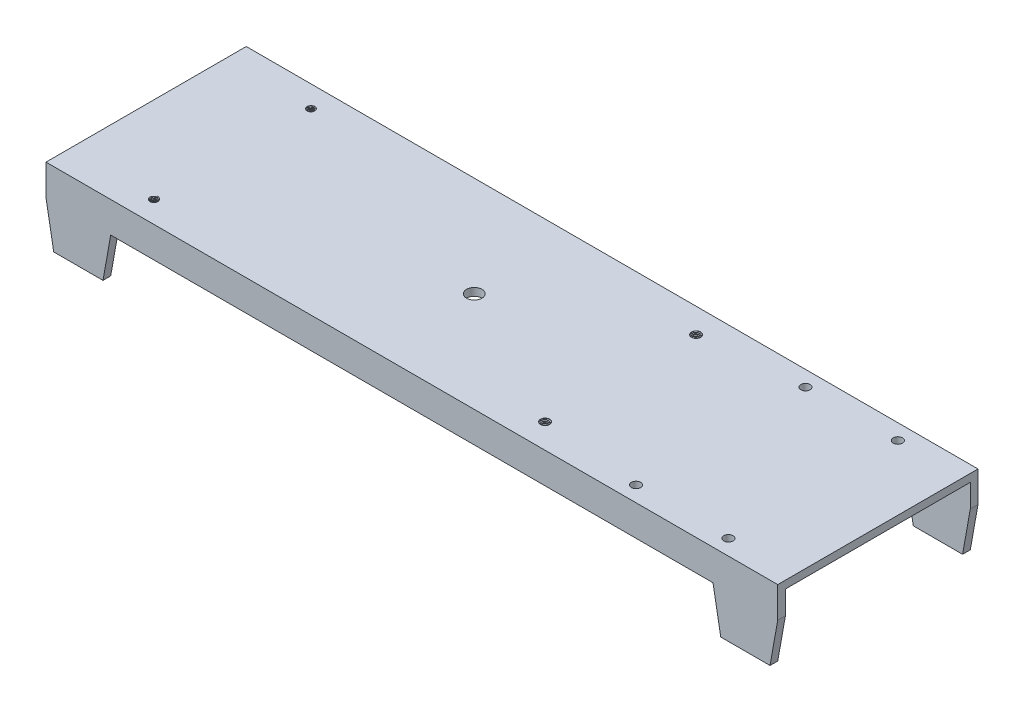
SolidWorks part; units mm, degrees
ref_plane "Front Plane" through (0, 0, 0) normal (0, 0, 1) x (1, 0, 0)
ref_plane "Top Plane" through (0, 0, 0) normal (0, 1, 0) x (1, 0, 0)
ref_plane "Right Plane" through (0, 0, 0) normal (1, 0, 0) x (0, 0, -1)
sketch "Sketch1" plane through (0, 0, 0) normal (0, 0, 1) x (1, 0, 0)
  line L0 (-237.5, 0) -> (237.5, 0)
  line L1 (237.5, 0) -> (237.5, -20)
  line L2 (237.5, -20) -> (232.5, -48)
  line L3 (232.5, -48) -> (200.5, -48)
  line L4 (200.5, -48) -> (195.5, -20)
  line L5 (195.5, -20) -> (-195.5, -20)
  line L6 (0, 136.8884) -> (0, -128.9529) construction
  line L7 (-200.5, -48) -> (-195.5, -20)
  line L8 (-237.5, 0) -> (-237.5, -20)
  line L9 (-232.5, -48) -> (-200.5, -48)
  line L10 (-237.5, -20) -> (-232.5, -48)
  point P11 (0, -20)
  point P15 (0, 0)
  dimension "D1" = 475
  dimension "D2" = 20
  dimension "D3" = 28
  dimension "D4" = 32
  dimension "D5" = 5
  dimension "D6" = 5
  dimension "D7" = 20
extrude "Boss-Extrude1" add sketch "Sketch1" along normal blind 130
sketch "Sketch4" plane through (237.5, 0, 0) normal (1, 0, 0) x (0, 0, -1)
  line L0 (-130, 0) -> (0, 0) construction
  line L1 (-125, -5) -> (-5, -5)
  line L2 (-125, -5) -> (-125, -20)
  line L3 (-125, -20) -> (-5, -20)
  line L4 (-5, -5) -> (-5, -20)
  line L5 (0, -20) -> (0, 0) construction
  line L6 (-130, -20) -> (-130, 0) construction
  line L7 (-130, -20) -> (0, -20) construction
  dimension "D1" = 5
  dimension "D2" = 5
  dimension "D3" = 5
  dimension "D4" = 0
extrude "Cut-Extrude3" cut sketch "Sketch4" against normal through all
sketch "Sketch6" plane through (0, 0, 0) normal (1, 0, 0) x (0, 0, -1)
  line L0 (-130, -48) -> (0, -48) construction
  line L1 (-125, -20) -> (-5, -20)
  line L2 (-125, -20) -> (-125, -48)
  line L3 (-125, -48) -> (-5, -48)
  line L4 (-5, -20) -> (-5, -48)
  line L6 (0, -48) -> (0, -20) construction
  dimension "D1" = 5
extrude "Cut-Extrude4" cut sketch "Sketch6" against normal mid plane 500
sketch "Sketch7" plane through (0, 0, 0) normal (0, 1, 0) x (1, 0, 0)
  line L0 (237.5, -130) -> (237.5, 0) construction
  line L1 (237.5, 0) -> (-237.5, 0) construction
  circle A0 centre (135.5, -10) radius 3
  circle A1 centre (195.5, -10) radius 3
  circle A2 centre (195.5, -120) radius 3
  circle A3 centre (135.5, -120) radius 3
  dimension "D1" = 6
  dimension "D2" = 42
  dimension "D3" = 110
  dimension "D4" = 10
  dimension "D5" = 60
extrude "Cut-Extrude5" cut sketch "Sketch7" against normal through all
sketch "Sketch8" plane through (0, 0, 0) normal (0, 1, 0) x (1, 0, 0)
  line L0 (237.5, -130) -> (237.5, 0) construction
  line L1 (237.5, 0) -> (-237.5, 0) construction
  line L2 (237.5, -130) -> (-237.5, -130) construction
  line L3 (-237.5, -130) -> (-237.5, 0) construction
  circle A0 centre (70.5, -16) radius 3
  circle A1 centre (70.5, -114) radius 3
  circle A2 centre (-24.5, -65) radius 5
  circle A3 centre (-181.5, -14) radius 2.5
  circle A4 centre (-181.5, -116) radius 2.5
  dimension "D1" = 5
  dimension "D2" = 5
  dimension "D3" = 10
  dimension "D4" = 6
  dimension "D5" = 6
  dimension "D6" = 262
  dimension "D7" = 167
  dimension "D8" = 167
  dimension "D9" = 16
  dimension "D10" = 16
  dimension "D11" = 65
  dimension "D12" = 14
  dimension "D13" = 14
  dimension "D14" = 56
  dimension "D15" = 56
extrude "Cut-Extrude6" cut sketch "Sketch8" against normal through all
thread "Thread1" pitch 1 method extrude profile "Thread Profile1" start angle 0, offset 0, length 0, pitch 1, diameter 6
ref_plane "Plane1" through (67.5, 0, 114) normal (0, 0, 1) x (-1, 0, 0)
sketch "Thread Profile1" plane through (67.5, 0, 114) normal (0, 0, 1) x (-1, 0, 0)
  line L0 (0, 0) -> (0, 1) construction
  line L11 (0, 0) -> (0, 0.875)
  line L12 (0, 0.875) -> (-0.5413, 0.5625)
  line L13 (-0.5413, 0.5625) -> (-0.5413, 0.3125)
  line L15 (-0.5413, 0.3125) -> (0, 0)
  line L17 (-0.5413, 0.4375) -> (0, 0.4375) construction
  point P2 (0, 0)
  dimension "Pitch" = 1
  dimension "Profile_Angle" = 60
  dimension "Profile_Land" = 0.25
  dimension "Profile_Height" = 0.5413
thread "Thread2" pitch 1 method extrude profile "Thread Profile2" start angle 0, offset 0, length 0, pitch 1, diameter 6
ref_plane "Plane2" through (67.5, 0, 16) normal (0, 0, 1) x (-1, 0, 0)
sketch "Thread Profile2" plane through (67.5, 0, 16) normal (0, 0, 1) x (-1, 0, 0)
  line L0 (0, 0) -> (0, 1) construction
  line L11 (0, 0) -> (0, 0.875)
  line L12 (0, 0.875) -> (-0.5413, 0.5625)
  line L13 (-0.5413, 0.5625) -> (-0.5413, 0.3125)
  line L15 (-0.5413, 0.3125) -> (0, 0)
  line L17 (-0.5413, 0.4375) -> (0, 0.4375) construction
  point P2 (0, 0)
  dimension "Pitch" = 1
  dimension "Profile_Angle" = 60
  dimension "Profile_Land" = 0.25
  dimension "Profile_Height" = 0.5413
thread "Thread3" pitch 0.8 method extrude profile "Thread Profile3" start angle 0, offset 0, length 0, pitch 0.8, diameter 5
ref_plane "Plane3" through (-184, 0, 14) normal (0, 0, 1) x (-1, 0, 0)
sketch "Thread Profile3" plane through (-184, 0, 14) normal (0, 0, 1) x (-1, 0, 0)
  line L0 (0, 0) -> (0, 0.8) construction
  line L11 (0, 0) -> (0, 0.7)
  line L12 (0, 0.7) -> (-0.433, 0.45)
  line L13 (-0.433, 0.45) -> (-0.433, 0.25)
  line L15 (-0.433, 0.25) -> (0, 0)
  line L17 (-0.433, 0.35) -> (0, 0.35) construction
  point P2 (0, 0)
  dimension "Pitch" = 0.8
  dimension "Profile_Angle" = 60
  dimension "Profile_Land" = 0.2
  dimension "Profile_Height" = 0.433
thread "Thread4" pitch 0.8 method extrude profile "Thread Profile4" start angle 0, offset 0, length 0, pitch 0.8, diameter 5
ref_plane "Plane4" through (-179, -5, 116) normal (0, 0, 1) x (1, 0, 0)
sketch "Thread Profile4" plane through (-179, -5, 116) normal (0, 0, 1) x (1, 0, 0)
  line L0 (0, 0) -> (0, 0.8) construction
  line L11 (0, 0) -> (0, 0.7)
  line L12 (0, 0.7) -> (-0.433, 0.45)
  line L13 (-0.433, 0.45) -> (-0.433, 0.25)
  line L15 (-0.433, 0.25) -> (0, 0)
  line L17 (-0.433, 0.35) -> (0, 0.35) construction
  point P2 (0, 0)
  dimension "Pitch" = 0.8
  dimension "Profile_Angle" = 60
  dimension "Profile_Land" = 0.2
  dimension "Profile_Height" = 0.433
